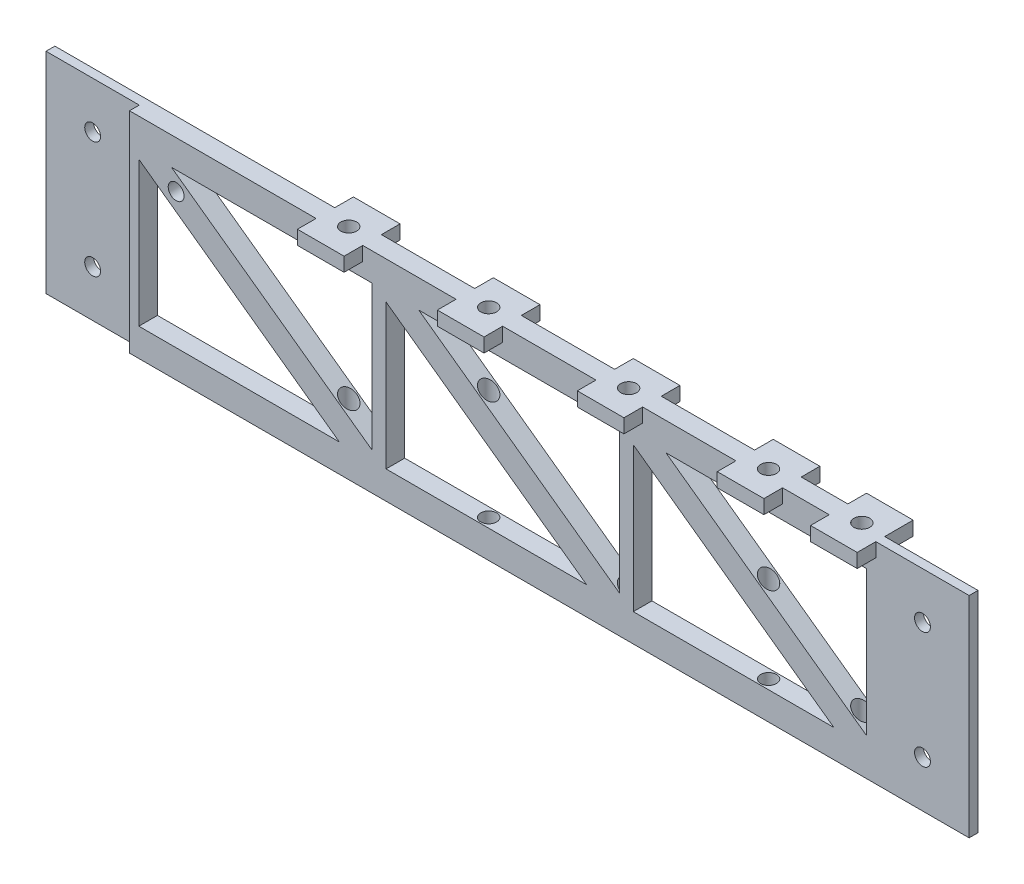
SolidWorks part; units mm, degrees
ref_plane "前视基准面" through (0, 0, 0) normal (0, 0, 1) x (1, 0, 0)
ref_plane "上视基准面" through (0, 0, 0) normal (0, 1, 0) x (1, 0, 0)
ref_plane "右视基准面" through (0, 0, 0) normal (1, 0, 0) x (0, 0, -1)
other "Configuration Table"
sketch "草图1" plane through (0, 0, 0) normal (0, 0, 1) x (1, 0, 0)
  line L1 (0, 0) -> (200, 0)
  line L2 (0, 0) -> (0, 45)
  line L3 (0, 45) -> (200, 45)
  line L4 (200, 0) -> (200, 45)
  dimension "D1" = 200
  dimension "D2" = 45
extrude "45高4厚桁架毛坯" add sketch "草图1" along normal blind 4
sketch "草图2" plane through (0, 0, 0) normal (0, 0, 1) x (1, 0, 0)
  line L0 (22, 6) -> (65, 6)
  line L1 (65, 6) -> (22, 37)
  line L2 (22, 37) -> (22, 6)
  line L3 (29, 39) -> (72, 8)
  line L4 (72, 8) -> (72, 39)
  line L5 (72, 39) -> (29, 39)
  line L6 (75, 6) -> (118, 6)
  line L7 (118, 6) -> (75, 37)
  line L8 (75, 37) -> (75, 6)
  line L9 (82, 39) -> (125, 8)
  line L10 (125, 8) -> (125, 39)
  line L11 (125, 39) -> (82, 39)
  line L12 (128, 6) -> (171, 6)
  line L13 (171, 6) -> (128, 37)
  line L14 (128, 37) -> (128, 6)
  line L15 (135, 39) -> (178, 8)
  line L16 (178, 8) -> (178, 39)
  line L17 (178, 39) -> (135, 39)
  dimension "D1" = 22
  dimension "D2" = 29
  dimension "D3" = 65
  dimension "D4" = 75
  dimension "D5" = 82
  dimension "D6" = 128
  dimension "D7" = 135
  dimension "D8" = 6
  dimension "D9" = 8
  dimension "D10" = 37
extrude "六个三角减重窗" cut sketch "草图2" against normal through all and the other way through all
sketch "草图3" plane through (0, 0, 0) normal (0, 1, 0) x (1, 0, 0)
  line L1 (0, -4) -> (20, -4)
  line L2 (0, -4) -> (0, -1.9)
  line L3 (0, -1.9) -> (20, -1.9)
  line L4 (20, -4) -> (20, -1.9)
  line L6 (180, -2.1) -> (200, -2.1)
  line L7 (180, -2.1) -> (180, 0)
  line L8 (180, 0) -> (200, 0)
  line L9 (200, -2.1) -> (200, 0)
  dimension "D1" = 20
  dimension "D2" = 180
  dimension "D3" = 1.9
  dimension "D4" = 2.1
extrude "始末端半厚搭接" cut sketch "草图3" against normal through all and the other way through all
sketch "草图4" plane through (0, 0, 0) normal (0, 0, 1) x (1, 0, 0)
  circle A0 centre (10, 10) radius 1.7
  circle A1 centre (10, 35) radius 1.7
  circle A2 centre (30, 10) radius 1.7
  circle A3 centre (30, 35) radius 1.7
  circle A4 centre (190, 10) radius 1.7
  circle A5 centre (190, 35) radius 1.7
  dimension "D1" = 3.4
  dimension "D2" = 10
  dimension "D3" = 30
  dimension "D4" = 190
  dimension "D5" = 10
  dimension "D6" = 35
extrude "搭接与梁根3p4孔" cut sketch "草图4" against normal through all and the other way through all
sketch "草图5" plane through (0, 0, 0) normal (0, 0, 1) x (1, 0, 0)
  line L1 (60, 42) -> (70, 42)
  line L2 (60, 42) -> (60, 45)
  line L3 (60, 45) -> (70, 45)
  line L4 (70, 42) -> (70, 45)
  line L6 (90, 42) -> (100, 42)
  line L7 (90, 42) -> (90, 45)
  line L8 (90, 45) -> (100, 45)
  line L9 (100, 42) -> (100, 45)
  line L11 (120, 42) -> (130, 42)
  line L12 (120, 42) -> (120, 45)
  line L13 (120, 45) -> (130, 45)
  line L14 (130, 42) -> (130, 45)
  line L16 (150, 42) -> (160, 42)
  line L17 (150, 42) -> (150, 45)
  line L18 (150, 45) -> (160, 45)
  line L19 (160, 42) -> (160, 45)
  line L21 (170, 42) -> (180, 42)
  line L22 (170, 42) -> (170, 45)
  line L23 (170, 45) -> (180, 45)
  line L24 (180, 42) -> (180, 45)
  dimension "D1" = 60
  dimension "D2" = 70
  dimension "D3" = 90
  dimension "D4" = 120
  dimension "D5" = 150
  dimension "D6" = 170
  dimension "D7" = 42
  dimension "D8" = 45
extrude "顶面局部固定耳" add sketch "草图5" along normal blind 12 from offset 4 offset against normal yes
sketch "草图6" plane through (0, 0, 0) normal (0, 1, 0) x (1, 0, 0)
  circle A0 centre (65, -2) radius 1.7
  circle A1 centre (95, -2) radius 1.7
  circle A2 centre (125, -2) radius 1.7
  circle A3 centre (155, -2) radius 1.7
  circle A4 centre (175, -2) radius 1.7
  dimension "D1" = 3.4
  dimension "D2" = 65
  dimension "D3" = 95
  dimension "D4" = 125
  dimension "D5" = 155
  dimension "D6" = 175
  dimension "D7" = 2
extrude "顶面固定耳3p4孔" cut sketch "草图6" against normal through all and the other way through all
